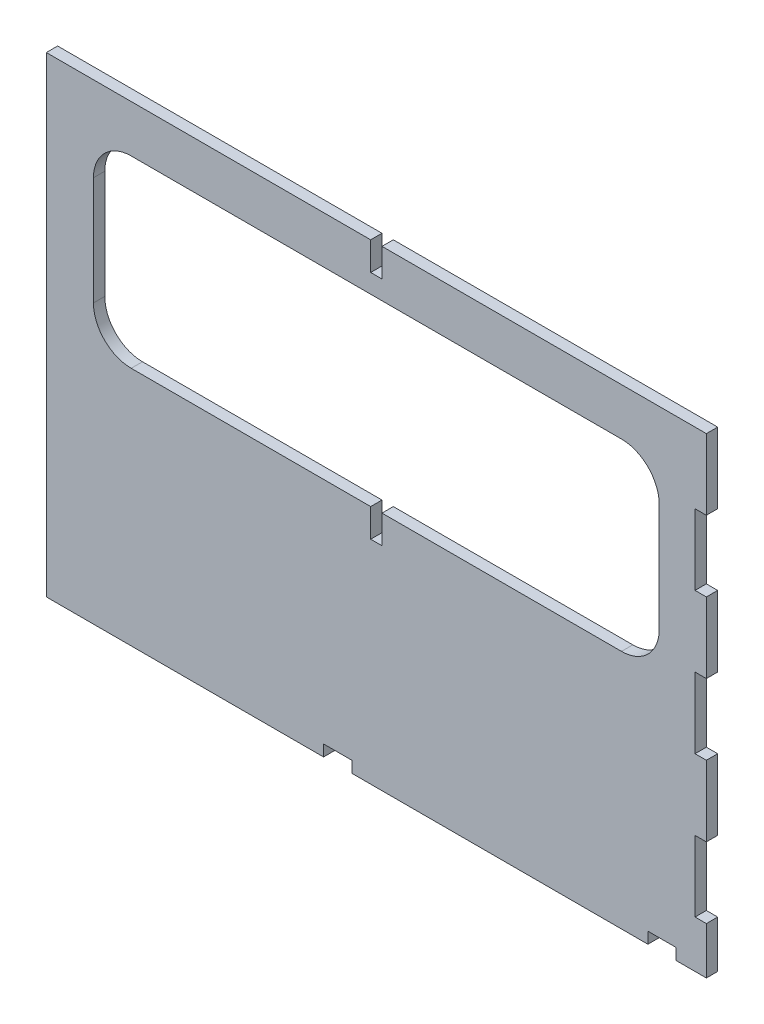
SolidWorks part; units mm, degrees
ref_plane "Front" through (0, 0, 0) normal (0, 0, 1) x (1, 0, 0)
ref_plane "Top" through (0, 0, 0) normal (0, 1, 0) x (1, 0, 0)
ref_plane "Right" through (0, 0, 0) normal (1, 0, 0) x (0, 0, -1)
sketch "Sketch1" plane through (0, 0, 0) normal (0, 0, 1) x (1, 0, 0)
  line L1 (0, 0) -> (-200, 0)
  line L2 (0, 0) -> (0, 150)
  line L4 (-200, 0) -> (-200, 150)
  line L5 (-100, 90) -> (-100, 0) construction
  line L6 (-175, 110) -> (-175, 125)
  line L7 (-25, 110) -> (-25, 125)
  line L9 (-175, 125) -> (-25, 125)
  line L11 (-200, 150) -> (0, 150)
  arc A0 (-153.0972, 57.0313) -> (-46.9028, 57.0312) centre (-100, 90) ccw
  arc A1 (-175, 110) -> (-153.0972, 57.0313) centre (-100, 110) ccw
  arc A2 (-46.9028, 57.0312) -> (-25, 110) centre (-100, 110) ccw
  dimension "D3" = 62.5
  dimension "D4" = 75
  dimension "D1" = 200
  dimension "D2" = 25
  dimension "D5" = 20
  dimension "D6" = 90
  dimension "D7" = 150
extrude "Boss-Extrude1" add sketch "Sketch1" along normal blind 6
sketch "Sketch3" plane through (0, 0, 6) normal (0, 0, 1) x (1, 0, 0)
  line L0 (-200, 150) -> (-200, 0) construction
  line L1 (-100, 27.5) -> (-200, 27.5)
  line L2 (-100, 27.5) -> (-100, 125)
  line L3 (-100, 125) -> (-200, 125)
  line L4 (-200, 27.5) -> (-200, 125)
  line L7 (-25, 125) -> (-175, 125) construction
  arc A0 (-153.0972, 57.0313) -> (-46.9028, 57.0312) centre (-100, 90) ccw construction
extrude "Cut-Extrude1" cut sketch "Sketch3" against normal blind 6
sketch "Sketch4" plane through (0, 0, 6) normal (0, 0, 1) x (1, 0, 0)
  line L0 (-250, 110) -> (-100, 110) construction
  line L1 (-100, 90) -> (-250, 90) construction
  line L2 (-250, 90) -> (-250, 110) construction
  line L3 (-25, 125) -> (0, 125) construction
  line L4 (-200, 27.5) -> (-250, 27.5)
  line L5 (-200, 27.5) -> (-200, 0)
  line L6 (-200, 0) -> (-350, 0)
  line L9 (-350, 0) -> (-350, 150)
  line L11 (-325, 110) -> (-325, 125)
  line L12 (-200, 125) -> (-325, 125)
  line L13 (-200, 125) -> (-200, 150)
  line L14 (-200, 150) -> (-350, 150)
  line L16 (0, 0) -> (0, 150) construction
  line L17 (-325, 125) -> (-350, 125) construction
  line L18 (-200, 0) -> (0, 0) construction
  arc A0 (-325, 110) -> (-303.0972, 57.0312) centre (-250, 110) ccw
  circle A1 centre (-100, 90) radius 62.5 construction
  circle A2 centre (-100, 110) radius 75 construction
  arc A3 (-46.9028, 57.0312) -> (-25, 110) centre (-100, 110) ccw construction
  arc A4 (-100, 27.5) -> (-46.9028, 57.0312) centre (-100, 90) ccw construction
  arc A5 (-303.0972, 57.0312) -> (-250, 27.5) centre (-250, 90) ccw
  dimension "D1" = 150
  dimension "D2" = 125
  dimension "D4" = 125
  dimension "D3" = 150
extrude "Boss-Extrude3" add sketch "Sketch4" against normal blind 6
sketch "Sketch5" plane through (0, 0, 6) normal (0, 0, 1) x (1, 0, 0)
  line L1 (-178, 150) -> (-172, 150)
  line L2 (-178, 150) -> (-178, 135)
  line L3 (-178, 135) -> (-172, 135)
  line L4 (-172, 150) -> (-172, 135)
  line L5 (-250, 27.5) -> (-100, 27.5) construction
  line L6 (-178, 27.5) -> (-172, 27.5)
  line L7 (-178, 27.5) -> (-178, 12.5)
  line L8 (-178, 12.5) -> (-172, 12.5)
  line L9 (-172, 27.5) -> (-172, 12.5)
  line L10 (0, 150) -> (-350, 150) construction
  point P12 (-175, 150)
  point P14 (-175, 150)
  dimension "D1" = 6
  dimension "D2" = 15
extrude "Cut-Extrude2" cut sketch "Sketch5" against normal blind 6
sketch "Sketch6" plane through (0, 0, 6) normal (0, 0, 1) x (1, 0, 0)
  line L0 (0, 0) -> (0, 150) construction
  line L1 (0, 112.5) -> (-6, 112.5)
  line L2 (0, 112.5) -> (0, 75)
  line L3 (0, 75) -> (-6, 75)
  line L4 (-6, 112.5) -> (-6, 75)
  line L5 (0, 150) -> (-172, 150) construction
  dimension "D1" = 37.5
  dimension "6" = 6
  dimension "D2" = 37.5
extrude "Cut-Extrude3" cut sketch "Sketch6" against normal blind 6
sketch "Sketch8" plane through (0, 0, 6) normal (0, 0, 1) x (1, 0, 0)
  line L1 (-350, 0) -> (0, 0)
  line L2 (-350, 0) -> (-350, -100)
  line L3 (-350, -100) -> (0, -100)
  line L4 (0, 0) -> (0, -100)
  dimension "D1" = 100
extrude "Boss-Extrude4" add sketch "Sketch8" against normal up to surface (6 mm away) up to face at (-117.6667, 103.75, 0)
pattern_linear "LPattern1" count 3 spacing 75 along (0, -1, 0) of "Cut-Extrude3"
sketch "Sketch7" plane through (0, 0, 6) normal (0, 0, 1) x (1, 0, 0)
  line L1 (-16, -100) -> (-31, -100)
  line L2 (-16, -100) -> (-16, -94)
  line L3 (-16, -94) -> (-31, -94)
  line L4 (-31, -100) -> (-31, -94)
  line L5 (-6, -37.5) -> (-6, -75) construction
  line L6 (-350, -100) -> (0, -100) construction
  line L7 (-178, 27.5) -> (-178, 12.5) construction
  line L8 (-188, -100) -> (-203, -100)
  line L9 (-188, -100) -> (-188, -94)
  line L10 (-188, -94) -> (-203, -94)
  line L11 (-203, -100) -> (-203, -94)
  dimension "D1" = 15
  dimension "D2" = 10
  dimension "D3" = 6
  dimension "D4" = 10
extrude "s" cut sketch "Sketch7" against normal through all
sketch "Sketch9" plane through (0, 0, 6) normal (0, 0, 1) x (1, 0, 0)
  line L0 (-25, 110) -> (-25, 125) construction
  line L1 (-325, 125) -> (-25, 125)
  line L2 (-325, 125) -> (-325, 27.5)
  line L3 (-325, 27.5) -> (-25, 27.5)
  line L4 (-25, 125) -> (-25, 27.5)
  line L5 (-250, 27.5) -> (-178, 27.5) construction
extrude "Cut-Extrude4" cut sketch "Sketch9" against normal through all
fillet "Fillet1" radius 20 4 edges at (-25, 27.5, 3) (-25, 125, 3) (-325, 27.5, 3) (-325, 125, 3)
